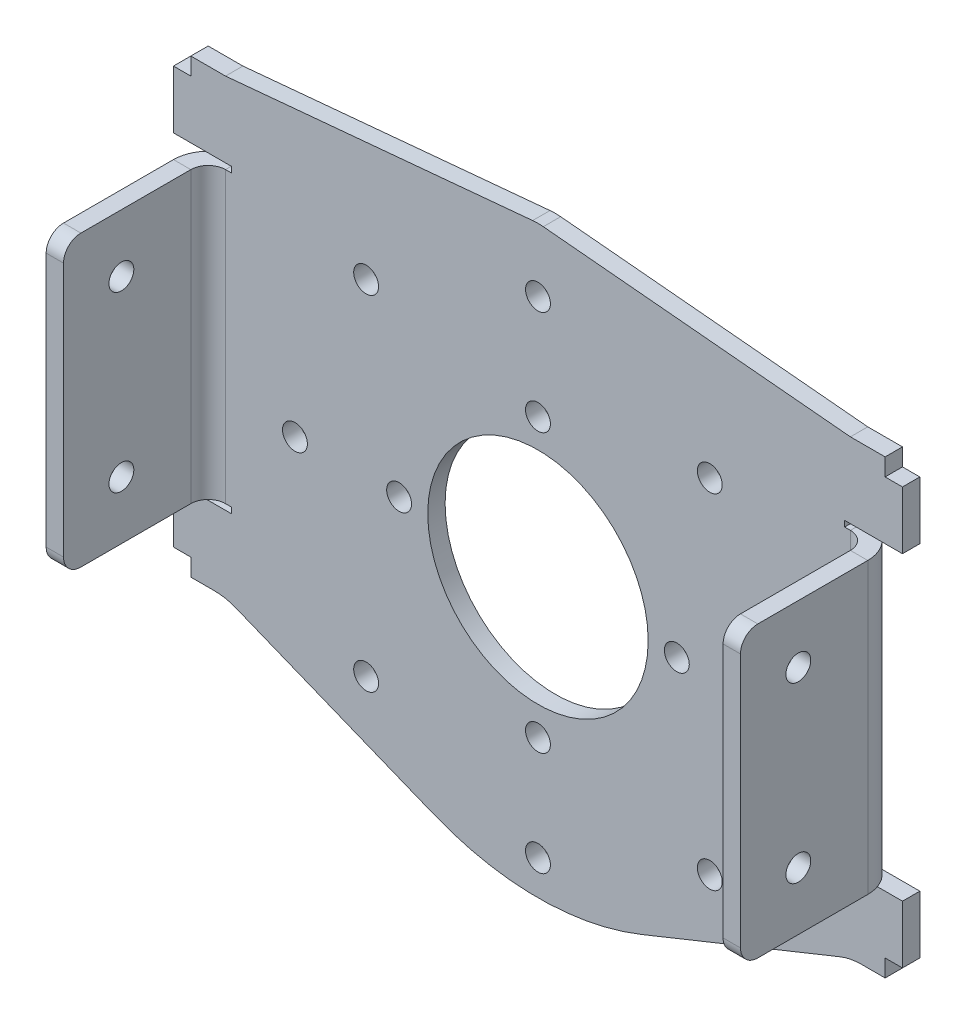
SolidWorks part; units mm, degrees
note: The reader was unsure of these and kept them because the rebuilt part matched: flange length of "UP".
other "Markup1"
sketch "Sketch20" plane through (-63.5, 48, 15) normal (-0.7144, 0.1948, 0.6721) x (0.6993, 0.1649, 0.6955)
material "3.3549 (EN-AW 5182)"
ref_plane "Front Plane" through (0, 0, 0) normal (0, 0, 1) x (1, 0, 0)
ref_plane "Top Plane" through (0, 0, 0) normal (0, 1, 0) x (1, 0, 0)
ref_plane "Right Plane" through (0, 0, 0) normal (1, 0, 0) x (0, 0, -1)
sketch "Sketch1" plane through (0, 0, 0) normal (0, 0, 1) x (1, 0, 0)
  line L14 (0, -44.7868) -> (0, 44.7868) construction
  line L21 (-54, -30) -> (-17.9304, -44.5253)
  line L23 (54, -30) -> (17.9304, -44.5253)
  line L24 (54, -30) -> (60, -30)
  line L25 (-54, 48) -> (-60, 48)
  line L26 (-60, 48) -> (-60, 45)
  line L27 (-60, 45) -> (-63, 45)
  line L28 (-63, 45) -> (-63, 35)
  line L34 (-53, -17) -> (-53, -16)
  line L35 (-53, -16) -> (-54, -16)
  line L36 (-54, -16) -> (-54, 34)
  line L37 (-54, 34) -> (-53, 34)
  line L38 (-53, 34) -> (-53, 35)
  line L40 (-54, -30) -> (-60, -30)
  line L41 (-60, -30) -> (-60, -27)
  line L42 (-60, -27) -> (-63, -27)
  line L43 (-63, -27) -> (-63, -17)
  line L44 (-63, 35) -> (-53, 35)
  line L45 (-63, -17) -> (-53, -17)
  line L46 (54, 48) -> (60, 48)
  line L47 (60, 48) -> (60, 45)
  line L48 (60, -30) -> (60, -27)
  line L49 (63, -17) -> (53, -17)
  line L50 (63, 35) -> (53, 35)
  line L51 (63, -27) -> (63, -17)
  line L52 (60, -27) -> (63, -27)
  line L53 (53, 34) -> (53, 35)
  line L54 (54, 34) -> (53, 34)
  line L55 (54, -16) -> (54, 34)
  line L56 (53, -16) -> (54, -16)
  line L57 (53, -17) -> (53, -16)
  line L58 (63, 45) -> (63, 35)
  line L59 (60, 45) -> (63, 45)
  line L60 (-54, -30) -> (-54, 48) construction
  line L61 (-54, 48) -> (0, 53)
  line L62 (0, 53) -> (54, 48)
  line L63 (55, 0) -> (-55, 0) construction
  arc A0 (-17.9304, -44.5253) -> (17.9304, -44.5253) centre (0, 0) ccw
  circle A1 centre (0, 0) radius 19.05
  circle A2 centre (0, 24) radius 1
  circle A9 centre (0, -42) radius 1
  circle A10 centre (-29.6985, -29.6985) radius 1
  circle A11 centre (-42, 0) radius 1
  circle A12 centre (-29.6985, 29.6985) radius 1
  circle A13 centre (0, 42) radius 1
  circle A14 centre (29.6985, 29.6985) radius 1
  circle A15 centre (42, 0) radius 1
  circle A16 centre (29.6985, -29.6985) radius 1
  circle A17 centre (24, 0) radius 1
  circle A18 centre (0, -24) radius 1
  circle A19 centre (-24, 0) radius 1
  point P32 (0, 0)
  point P35 (0, 0)
  point P54 (0, 0)
  dimension "D1" = 48
  dimension "D6" = 38.1
  dimension "D8" = 2
  dimension "D13" = 30
  dimension "D14" = 2
  dimension "D2" = 54
  dimension "D3" = 4
  dimension "D4" = 5
  dimension "D5" = 10
  dimension "D7" = 48
  dimension "D9" = 24
  dimension "D11" = 1
  dimension "D12" = 1
  dimension "D15" = 42
  dimension "D17" = 3
  dimension "D18" = 6
  dimension "D10" = 10
  dimension "D19" = 3
  dimension "D20" = 1
  dimension "D21" = 3
  dimension "D16" = 8
base flange "Base-Flange1" sketch "Sketch1" thickness 3 reverse thickness direction no parameters "D1"=3
edge flange "UP" sketch "Sketch27" flange angle 90 flange length 28 flange position bend outside bend radius 3 thickness 3 relief rectangular parameters "D1"=2.5, "D6"=10
bend "EdgeBend4" bend radius 3 bend angle 90 parameters "D5"=1
sketch "Sketch27" plane through (-54, 0, 0) normal (1, 0, 0) x (0, 1, 0)
  line L0 (34, 0) -> (-16, 0) construction
  line L1 (34, 0) -> (-16, 0)
  line L2 (34, 0) -> (34, 25)
  line L3 (34, 25) -> (-16, 25)
  line L4 (-16, 25) -> (-16, 0)
  line L5 (-16, 15) -> (34, 15) construction
  circle A0 centre (-6, 15) radius 1
  circle A2 centre (24, 15) radius 1
  dimension "D2" = 2
  dimension "D3" = 15
  dimension "D4" = 10
  dimension "D1" = 25
  dimension "D5" = 10
mirror "Mirror1" about plane through (0, 0, 0) normal (1, 0, 0) of "UP"
bend "MirrorBend3" bend radius 3 bend angle 90 parameters "D5"=7
sketch "Sketch16" plane through (0, 0, 0) normal (0, 0, 1) x (1, 0, 0)
  point P0 (0, 24)
  point P3 (24, 0)
  point P6 (-24, 0)
  point P9 (0, -24)
  point P12 (0, -42)
  point P15 (29.6985, -29.6985)
  point P18 (42, 0)
  point P21 (29.6985, 29.6985)
  point P24 (0, 42)
  point P27 (-29.6985, 29.6985)
  point P30 (-42, 0)
  point P33 (-29.6985, -29.6985)
hole_wizard "M4 Clearance Hole1" positions "Sketch16" profile "Sketch15" hole size "M4" standard "ANSI Metric"
sketch "Sketch15" plane through (0, 24, 0) normal (1, 0, 0) x (0, -1, 0)
  line L0 (0, 0) -> (0, 137.2919)
  line L1 (0, 137.2919) -> (2.15, 136)
  line L2 (2.15, 136) -> (2.15, 0)
  line L5 (2.15, 0) -> (0, 0)
  line L10 (0, 137.2919) -> (-2.15, 136) construction
  line L11 (0, -6.35) -> (0, 107.95) construction
  dimension "Hole Dia." = 4.3
  dimension "Hole Depth" = 136
  dimension "Drill Angle" = 118
sketch "Sketch30" plane through (-60, 0, 0) normal (-1, 0, 0) x (0, 0, 1)
  point P0 (15, 24)
  point P6 (15, -6)
hole_wizard "M4 Clearance Hole2" positions "Sketch30" profile "Sketch29" hole size "M4" standard "ANSI Metric"
sketch "Sketch29" plane through (-60, 24, 15) normal (0, 1, 0) x (0, 0, 1)
  line L0 (0, 0) -> (0, 137.2919)
  line L1 (0, 137.2919) -> (2.15, 136)
  line L2 (2.15, 136) -> (2.15, 0)
  line L5 (2.15, 0) -> (0, 0)
  line L10 (0, 137.2919) -> (-2.15, 136) construction
  line L11 (0, -6.35) -> (0, 107.95) construction
  dimension "Hole Dia." = 4.3
  dimension "Hole Depth" = 136
  dimension "Drill Angle" = 118
fillet "Fillet1" radius 10 3 edges at (-54, -30, -1.5) (54, -30, -1.5) (0, 53, -1.5)
fillet "Fillet2" radius 3 4 edges at (-58.5, 34, 25) (-58.5, -16, 25) (58.5, -16, 25) (58.5, 34, 25)
sketch "Bend-Lines1" [suppressed] plane through (0, 0, 0) normal (0, 1, 0) x (1, 0, 0)
sketch "Bounding-Box1" [suppressed] plane through (0, 0, 0) normal (0, 1, 0) x (1, 0, 0)
sheet metal parameters "Sheet-Metal8" thickness 3 parameters "D1"=4
flat pattern "Flat-Pattern8" [suppressed]
sketch "Bend-Lines2" plane through (0, 0, 0) normal (0, 1, 0) x (1, 0, 0)
sketch3d "Bounding-Box2" [suppressed]
  line L0 (-57.9979, 48.0031, 0) -> (58.0001, 47.9999, 0) construction
  line L1 (-58.0006, -47.9984, 0) -> (57.9974, -48.0016, 0) construction
  line L2 (-57.9979, 48.0031, 0) -> (-58.0006, -47.9984, 0) construction
  line L3 (58.0001, 47.9999, 0) -> (57.9974, -48.0016, 0) construction
sheet metal parameters "Sheet-Metal9" thickness 3 parameters "D1"=4
flat pattern "Flat-Pattern8"
sketch "Bend-Lines2" plane through (0, 0, 0) normal (0, 0, 1) x (1, 0, 0)
  line L2 (-57.3197, 34) -> (-57.3197, -16) construction
  line L3 (-57.3197, 34) -> (-57.3197, -16) construction
  point P0 (-60.3197, 135)
  point P1 (-60.3197, 105)
sketch3d "Bounding-Box2" [suppressed]
  line L0 (-72.6394, -48, 0) -> (58, -48, 0) construction
  line L1 (-72.6394, 48, 0) -> (58, 48, 0) construction
  line L2 (-72.6394, -48, 0) -> (-72.6394, 48, 0) construction
  line L3 (58, -48, 0) -> (58, 48, 0) construction
bend of the flat pattern "Flatten-<EdgeBend4>1"
sheet metal parameters "Sheet-Metal11" thickness 3 parameters "D1"=4
flat pattern "Flat-Pattern8"
sketch "Bend-Lines2" plane through (0, 0, 0) normal (0, 0, 1) x (1, 0, 0)
  line L8 (57.3197, -16) -> (57.3197, 34) construction
  line L9 (-57.3197, 34) -> (-57.3197, -16) construction
  line L10 (57.3197, -16) -> (57.3197, 34) construction
  line L11 (-57.3197, 34) -> (-57.3197, -16) construction
  point P0 (-57.8197, 48)
  point P1 (-57.8197, 10)
  point P2 (-57.8197, 0)
  point P3 (-57.8197, -30)
  point P4 (57.8197, -30)
  point P5 (57.8197, 0)
  point P6 (57.8197, 10)
  point P7 (57.8197, 48)
sketch3d "Bounding-Box2" [suppressed]
  line L0 (-72.6394, -48, 0) -> (72.6394, -48, 0) construction
  line L1 (-72.6394, 48, 0) -> (72.6394, 48, 0) construction
  line L2 (-72.6394, -48, 0) -> (-72.6394, 48, 0) construction
  line L3 (72.6394, -48, 0) -> (72.6394, 48, 0) construction
bend of the flat pattern "Flatten-<EdgeBend4>2"
bend of the flat pattern "Flatten-<MirrorBend3>1"
sheet metal parameters "Sheet-Metal12" thickness 3 parameters "D1"=4
flat pattern "Flat-Pattern8"
sketch "Bend-Lines2" plane through (0, 0, 0) normal (0, 0, 1) x (1, 0, 0)
  line L8 (57.9635, -16) -> (57.9635, 34) construction
  line L9 (-57.9635, 34) -> (-57.9635, -16) construction
  line L10 (57.9635, -16) -> (57.9635, 34) construction
  line L11 (-57.9635, 34) -> (-57.9635, -16) construction
sketch3d "Bounding-Box2" [suppressed]
  line L0 (-83.927, -48, 0) -> (83.927, -48, 0) construction
  line L1 (-83.927, 53, 0) -> (83.927, 53, 0) construction
  line L2 (-83.927, -48, 0) -> (-83.927, 53, 0) construction
  line L3 (83.927, -48, 0) -> (83.927, 53, 0) construction
bend of the flat pattern "Flatten-<MirrorBend3>2"
bend of the flat pattern "Flatten-<EdgeBend4>3"
sheet metal parameters "Sheet-Metal14" thickness 3 parameters "D1"=4
flat pattern "Flat-Pattern8"
sketch "Bend-Lines2" plane through (0, 0, 0) normal (0, 0, 1) x (1, 0, 0)
  line L8 (57.1, -16) -> (57.1, 34) construction
  line L9 (-57.1, 34) -> (-57.1, -16) construction
  line L10 (57.1, -16) -> (57.1, 34) construction
  line L11 (-57.1, 34) -> (-57.1, -16) construction
sketch3d "Bounding-Box2" [suppressed]
  line L0 (-82.2, -48, 0) -> (82.2, -48, 0) construction
  line L1 (-82.2, 52.9572, 0) -> (82.2, 52.9572, 0) construction
  line L2 (-82.2, -48, 0) -> (-82.2, 52.9572, 0) construction
  line L3 (82.2, -48, 0) -> (82.2, 52.9572, 0) construction
bend of the flat pattern "Flatten-<MirrorBend3>2"
bend of the flat pattern "Flatten-<EdgeBend4>3"
